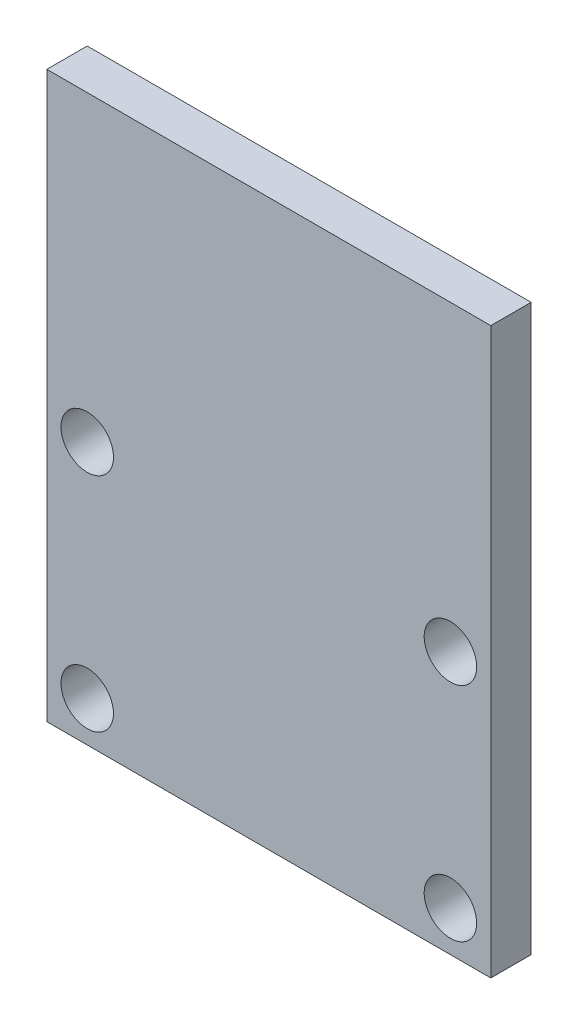
SolidWorks part; units mm, degrees
ref_plane "Front" through (0, 0, 0) normal (0, 0, 1) x (1, 0, 0)
ref_plane "Top" through (0, 0, 0) normal (0, 1, 0) x (1, 0, 0)
ref_plane "Right" through (0, 0, 0) normal (1, 0, 0) x (0, 0, -1)
sketch "草图1" plane through (0, 0, 0) normal (0, 0, 1) x (1, 0, 0)
  line L1 (-11, 14) -> (11, 14)
  line L2 (-11, 14) -> (-11, -14)
  line L3 (-11, -14) -> (11, -14)
  line L4 (11, 14) -> (11, -14)
  line L5 (0, -14) -> (0, 14) construction
  line L6 (-11, 0) -> (11, 0) construction
  line L7 (-9, -0.9979) -> (9, -0.9979) construction
  line L8 (-9, -0.9979) -> (-9, -11.9979) construction
  line L9 (-9, -11.9979) -> (9, -11.9979) construction
  line L10 (9, -0.9979) -> (9, -11.9979) construction
  line L11 (0, -11.9979) -> (0, -0.9979) construction
  line L12 (-9, -6.4979) -> (9, -6.4979) construction
  line L13 (-3, -9.4979) -> (3, -9.4979) construction
  line L14 (-3, -9.4979) -> (-3, -3.4979) construction
  line L15 (-3, -3.4979) -> (3, -3.4979) construction
  line L16 (3, -9.4979) -> (3, -3.4979) construction
  line L17 (-3, -9.4979) -> (3, -3.4979) construction
  line L18 (-3, -3.4979) -> (3, -9.4979) construction
  circle A0 centre (-9, -11.9979) radius 1.3
  circle A1 centre (-9, -0.9979) radius 1.3
  circle A2 centre (9, -0.9979) radius 1.3
  circle A3 centre (9, -11.9979) radius 1.3
  point P13 (0, -6.4979)
  point P21 (0, 0)
  point P22 (0, 0)
  point P70 (0, -6.4979)
  point P92 (0, 0)
  dimension "D5" = 2.6
  dimension "D6" = 2.6
  dimension "D7" = 2.6
  dimension "D8" = 2.6
  dimension "D1" = 22
  dimension "D2" = 28
  dimension "D3" = 11
  dimension "D4" = 18
  dimension "D9" = 0
  dimension "D10" = 0
extrude "凸台-拉伸1" add sketch "草图1" along normal blind 2
